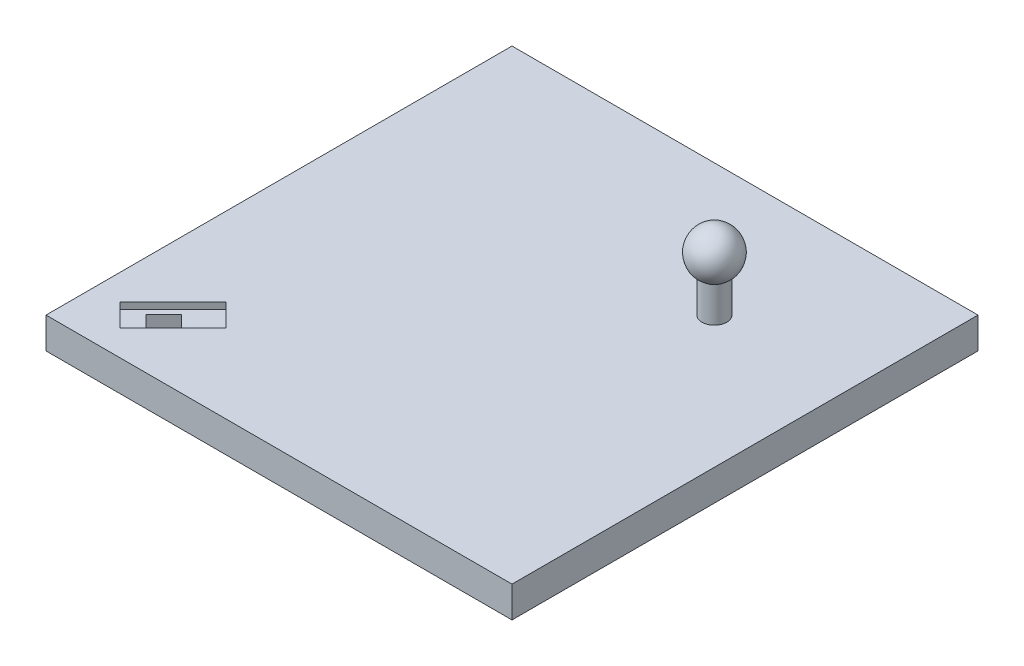
SolidWorks part; units mm, degrees
ref_plane "Front Plane" through (0, 0, 0) normal (0, 0, 1) x (1, 0, 0)
ref_plane "Top Plane" through (0, 0, 0) normal (0, 1, 0) x (1, 0, 0)
ref_plane "Right Plane" through (0, 0, 0) normal (1, 0, 0) x (0, 0, -1)
sketch "Sketch1" plane through (0, 0, 0) normal (0, 1, 0) x (1, 0, 0)
  line L1 (-75, -75) -> (75, -75)
  line L2 (-75, -75) -> (-75, 75)
  line L3 (-75, 75) -> (75, 75)
  line L4 (75, -75) -> (75, 75)
  line L5 (-75, -75) -> (75, 75) construction
  line L6 (-75, 75) -> (75, -75) construction
  point P0 (0, 0)
extrude "Boss-Extrude1" add sketch "Sketch1" along normal blind 10
sketch "Sketch2" plane through (0, 0, 75) normal (0, 0, 1) x (1, 0, 0)
  line L0 (-75, 10) -> (-75, 0)
ref_plane "Plane4" through (0, 0, 0) normal (0.7071, 0, 0.7071) x (0, -1, 0)
sketch "Sketch3" plane through (0, 0, 0) normal (0.7071, 0, 0.7071) x (0, -1, 0)
  line L0 (-10, -83.2779) -> (-4, -83.2779) construction
  line L1 (-10, -106.066) -> (-10, 0) construction
  line L2 (-4, -83.2779) -> (-4, -68.1779) construction
  line L3 (-4, -68.1779) -> (-6, -68.1779)
  line L4 (-6, -68.1779) -> (-6, -75.2779) construction
  line L5 (-6, -75.2779) -> (-8, -75.2779)
  line L6 (-8, -75.2779) -> (-8, -65.0779)
  line L7 (-8, -65.0779) -> (-10, -65.0779)
  line L8 (-10, -89.2779) -> (-10, -65.0779)
  line L9 (-4, -83.2779) -> (-8, -83.2779)
  line L10 (-8, -83.2779) -> (-8, -89.2779)
  line L11 (-8, -89.2779) -> (-10, -89.2779)
  line L12 (-6, -71.3779) -> (-6, -75.2779)
  line L13 (-4, -71.3779) -> (-4, -83.2779)
  arc A0 (-4, -68.1779) -> (-4, -71.3779) centre (-8.2059, -69.7779) cw
  arc A1 (-6, -68.1779) -> (-6, -71.3779) centre (-1.7941, -69.7779) ccw
  dimension "D2" = 3.2
  dimension "D1" = 3.2
extrude "Cut-Extrude1" cut sketch "Sketch3" against normal blind 3.1 and the other way blind 3.1
sketch "Sketch4" plane through (-2.192, 0, -2.192) normal (0.7071, 0, 0.7071) x (0.7071, 0, -0.7071)
  line L1 (-89.2779, 10) -> (-65.0779, 10)
  line L2 (-89.2779, 10) -> (-89.2779, 8)
  line L3 (-89.2779, 8) -> (-65.0779, 8)
  line L4 (-65.0779, 10) -> (-65.0779, 8)
extrude "Cut-Extrude2" cut sketch "Sketch4" against normal blind 2 and the other way blind 8.2
sketch "Sketch5" plane through (0, 0, 0) normal (0.7071, 0, 0.7071) x (0, -1, 0)
  line L0 (-36.9681, 46.066) -> (16.081, 46.066) construction
  line L1 (-10, 106.066) -> (0, 106.066) construction
  line L2 (-10, 46.066) -> (-35, 46.066)
  line L3 (-10, 0) -> (-10, 106.066) construction
  line L4 (-10, 50.066) -> (-21.3137, 50.066)
  line L5 (-10, 50.066) -> (-10, 46.066)
  circle A0 centre (-27.5037, 45.8312) radius 7.5 construction
  arc A1 (-35, 46.066) -> (-21.3137, 50.066) centre (-27.5037, 45.8312) cw
  dimension "D1" = 60
revolve "Revolve1" add sketch "Sketch5" angle 360 about L0
